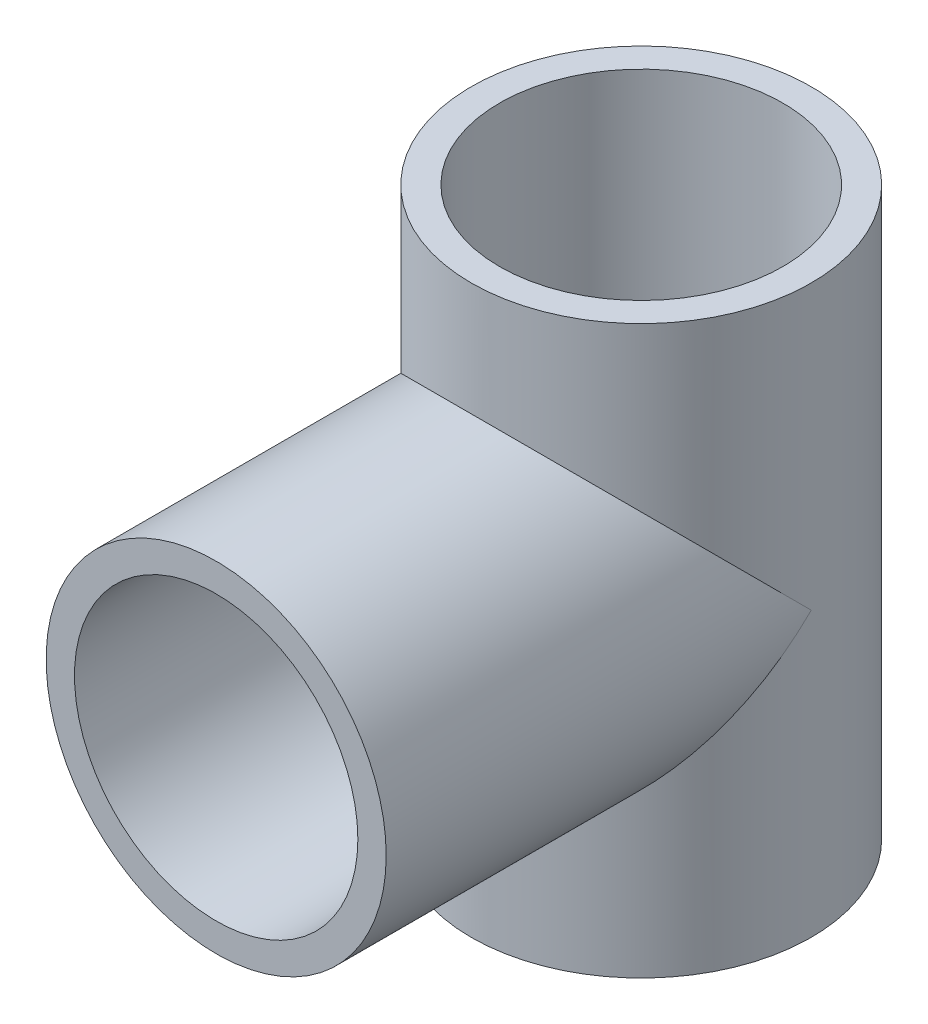
SolidWorks part; units mm, degrees
ref_plane "前视基准面" through (0, 0, 0) normal (0, 0, 1) x (1, 0, 0)
ref_plane "上视基准面" through (0, 0, 0) normal (0, 1, 0) x (1, 0, 0)
ref_plane "右视基准面" through (0, 0, 0) normal (1, 0, 0) x (0, 0, -1)
sketch "草图1" plane through (0, 0, 0) normal (0, 1, 0) x (1, 0, 0)
  circle A0 centre (0, 0) radius 10
  circle A1 centre (0, 0) radius 12
  dimension "D1" = 20
  dimension "D2" = 2
extrude "凸台-拉伸1" add sketch "草图1" along normal mid plane 40
sketch "草图2" plane through (0, 0, 0) normal (0, 0, 1) x (1, 0, 0)
  circle A0 centre (0, 0) radius 12
  circle A1 centre (0, 0) radius 10
  dimension "D1" = 20
  dimension "D2" = 2
extrude "凸台-拉伸2" add sketch "草图2" along normal blind 30
extrude "切除-拉伸1" cut sketch "草图2<2>" along normal blind 30 contours A1
sketch "草图2<2>" plane through (0, 0, 0) normal (0, 0, 1) x (1, 0, 0) same geometry as "草图2"
extrude "切除-拉伸2" cut sketch "草图1<2>" against normal mid plane 30 contours A0
sketch "草图1<2>" plane through (0, 0, 0) normal (0, 1, 0) x (1, 0, 0) same geometry as "草图1"
